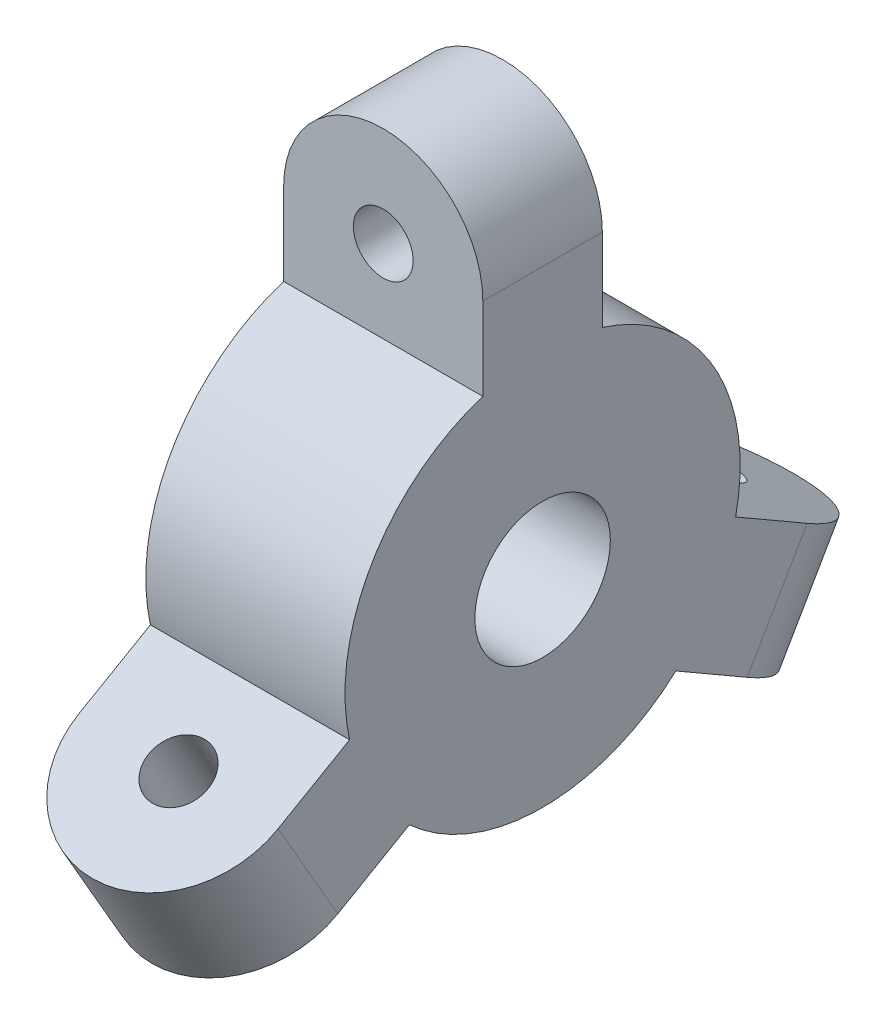
SolidWorks part; units mm, degrees
ref_plane "Plan de face" through (0, 0, 0) normal (0, 0, 1) x (1, 0, 0)
ref_plane "Plan de dessus" through (0, 0, 0) normal (0, 1, 0) x (1, 0, 0)
ref_plane "Plan de droite" through (0, 0, 0) normal (1, 0, 0) x (0, 0, -1)
sketch "Esquisse1" plane through (0, 0, 0) normal (1, 0, 0) x (0, 0, -1)
  line L0 (0, 0) -> (0, 18.6) construction
  line L1 (-3, 18.6) -> (3, 18.6)
  line L2 (-3, 18.6) -> (-3, 9.4555)
  line L3 (3, 18.6) -> (3, 9.4555)
  line L4 (17.6081, -6.7019) -> (9.6887, -2.1297)
  line L5 (17.6081, -6.7019) -> (14.6081, -11.8981)
  line L6 (14.6081, -11.8981) -> (6.6887, -7.3258)
  line L7 (-14.6081, -11.8981) -> (-6.6887, -7.3258)
  line L8 (-14.6081, -11.8981) -> (-17.6081, -6.7019)
  line L9 (-17.6081, -6.7019) -> (-9.6887, -2.1297)
  arc A0 (3, 9.4555) -> (9.6887, -2.1297) centre (0, 0) cw
  arc A1 (6.6887, -7.3258) -> (-6.6887, -7.3258) centre (0, 0) cw
  arc A2 (-9.6887, -2.1297) -> (-3, 9.4555) centre (0, 0) cw
  circle A3 centre (0, 0) radius 9.92 construction
  point P21 (0, 0)
  dimension "D4" = 9.92
  dimension "D1" = 18.6
  dimension "D2" = 6
  dimension "D3" = 3
extrude "Boss.-Extru.1" add sketch "Esquisse1" along normal blind 5 and the other way blind 5
hole_wizard "Trou taraudé M81" positions "Esquisse3" profile "Esquisse4" tap size "M8" standard "ISO" end condition through all
sketch "Esquisse3" plane through (5, 0, 0) normal (1, 0, 0) x (0, 0, -1)
  point P0 (0, 0)
sketch "Esquisse4" plane through (5, 0, 0) normal (0, 1, 0) x (0, 0, -1)
  line L0 (0, 0) -> (0, 10)
  line L1 (0, 10) -> (3.4, 10)
  line L2 (3.4, 10) -> (3.4, 0)
  line L5 (3.4, 0) -> (0, 0)
  line L11 (0, -6.35) -> (0, 107.95) construction
  dimension "Diamètre du trou pour taraudage jusqu'au prochain" = 6.8
  dimension "Profondeur du trou pour taraudage jusqu'au prochain" = 10
cosmetic thread "Filetage de perçage1" parameters "D2"=8
sketch "Esquisse5" plane through (0, 0, 3) normal (0, 0, 1) x (1, 0, 0)
  line L0 (0, 18.6) -> (0, 0) construction
  line L2 (-5, 9.4555) -> (-5, 13.6)
  line L3 (-5, 18.6) -> (-5, 9.4555) construction
  line L4 (-5, 9.4555) -> (-13.1992, 9.4555)
  line L5 (-13.1992, 9.4555) -> (-13.1992, 23.6)
  line L6 (-13.1992, 23.6) -> (13.6203, 23.6)
  line L7 (13.6203, 23.6) -> (13.6203, 9.4555)
  line L8 (13.6203, 9.4555) -> (5, 9.4555)
  line L9 (5, 9.4555) -> (5, 13.6)
  line L10 (5, 18.6) -> (5, 9.4555) construction
  line L11 (-5, 18.6) -> (5, 18.6) construction
  arc A1 (-5, 13.6) -> (5, 13.6) centre (0, 13.6) cw
  circle A2 centre (0, 13.6) radius 1.5
  dimension "D1" = 3
  dimension "D5" = 5
  dimension "D2" = 8.1992
  dimension "D3" = 8.6203
  dimension "D4" = 5
extrude "Enlèv. mat.-Extru.1" cut sketch "Esquisse5" against normal through all
pattern_circular "Répétition circulaire1" count 3 over 360 about axis through (5, 0, 0) along (1, 0, 0) of "Enlèv. mat.-Extru.1"
